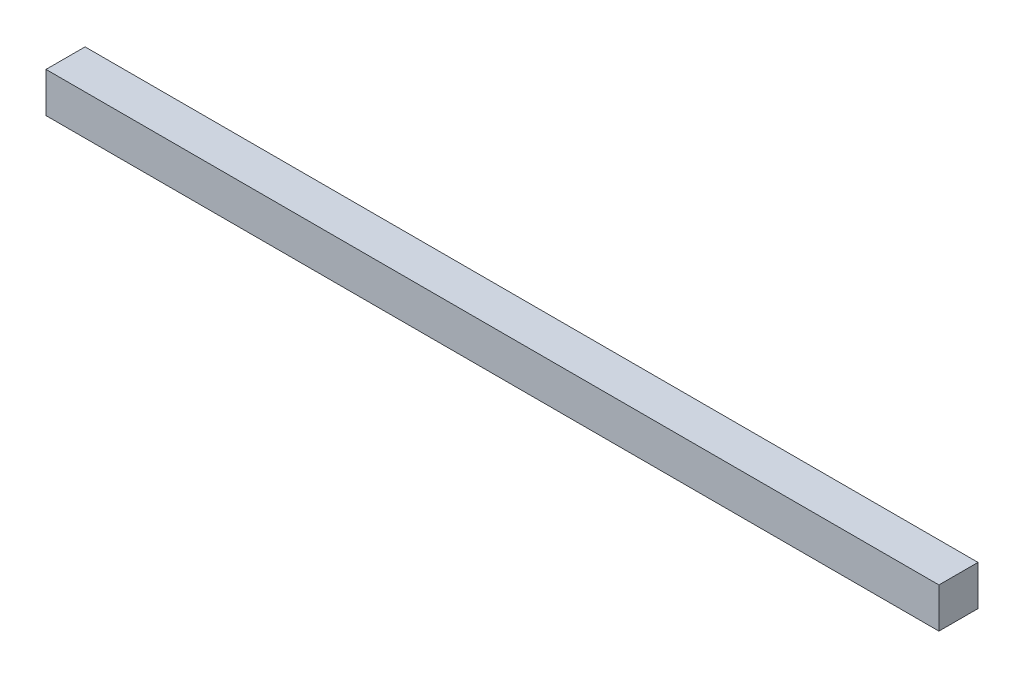
SolidWorks part; units mm, degrees
ref_plane "Спереди" through (0, 0, 0) normal (0, 0, 1) x (1, 0, 0)
ref_plane "Сверху" through (0, 0, 0) normal (0, 1, 0) x (1, 0, 0)
ref_plane "Справа" through (0, 0, 0) normal (1, 0, 0) x (0, 0, -1)
other "Configuration Table"
sketch "Ширина_фанера_плюс_зазор" plane through (0, 0, 0) normal (0, 0, 1) x (1, 0, 0)
  line L0 (-0.1, -3.075) -> (137.075, -3.075)
  line L1 (137.075, -3.075) -> (137.075, 3.075)
  line L2 (137.075, 3.075) -> (-0.1, 3.075)
  line L3 (-0.1, 3.075) -> (-0.1, -3.075)
  line L4 (-0.1, -3.075) -> (137.075, 3.075) construction
  point P4 (68.4875, 0)
  dimension "Ширина" = 137.175
  dimension "Глубина" = 6.15
  dimension "Положение_ПоОси" = 68.4875
extrude "Прямой_участок" add sketch "Ширина_фанера_плюс_зазор" along normal blind 6
equation "\"D1@Прямой_участок\" = \"Толщина тонких панелей\""
equation "\"Глубина@Ширина_фанера_плюс_зазор\"  = \"Толщина горизонтальных плит\"+\"Посадочный зазор\""
equation "\"Фанера\"= \"Толщина горизонтальных плит\""
equation "\"Ширина шипа\"=16"
equation "\"Межосевое шипов\"=40"
equation "\"Посадочный зазор\"=0.15"
equation "\"Основная фреза\"=6"
equation "\"Мелкая фреза\"=6"
equation "\"Запас разгрузки\"=0.05"
equation "\"Ширина образца\"=84"
equation "\"Высота образца\"=50"
equation "\"Канал М6\"=6"
equation "\"Гайка под ключ\"=10.3"
equation "\"Длина кармана гайки\"=6.2"
equation "\"Отступ гайки\"=12"
equation "\"Ширина@Ширина_фанера_плюс_зазор\" = (\"Глубина ячейки\"+3*\"Толщина тонких панелей\")/2+(\"Толщина вертикальных стенок\"+\"Посадочный зазор\")/2+0.1"
equation "\"Положение_ПоОси@Ширина_фанера_плюс_зазор\" = (\"Глубина ячейки\"+3*\"Толщина тонких панелей\")/4+(\"Толщина вертикальных стенок\"+\"Посадочный зазор\")/4-0.05"
equation "\"Ширина груза\"= 160"
equation "\"Глубина груза\"= 240"
equation "\"Высота груза\"= 160"
equation "\"Ширина ячейки\"= \"Ширина груза\" + 10"
equation "\"Глубина ячейки\"= \"Глубина груза\" + 10"
equation "\"Высота ячейки\"= \"Высота груза\" + 10 + 13"
equation "\"Колво ячеек ширина\"= 2"
equation "\"Колво ячеек высота\"= 2"
equation "\"Толщина стенки\"= \"Толщина тонких панелей\""
equation "\"Крепление дверцы\"= 5 "
equation "\"Ширина рейки\"= \"Толщина шестерни\""
equation "\"Высота рейки\"= 20"
equation "\"Высота пола\"= 2*\"Толщина тонких панелей\""
equation "\"Колво полозьев\"= 5"
equation "\"Отступ рейки\"= 20"
equation "\"Глубина каретки\"= \"Глубина ячейки\" + 30 + \"Мотор Y высота корпуса\" + 20"
equation "\"Длинна рейки\"= (\"Ширина ячейки\"+\"Толщина вертикальных стенок\"+\"Крепление дверцы\")*\"Колво ячеек ширина\"+\"Ширина ячейки выгрузки\"*\"Колво выгрузки\"+\"Толщина вертикальных стенок\"+2*\"Отступ крепления мотора фиксации\"-\"Крепление дверцы\"*\"Колво ячеек ширина\""
equation "\"Отступ шпильки\"= 26"
equation "\"Диаметр шпильки\"= 5"
equation "\"Длинна шпильки\"= (\"Высота ячейки\"+\"Толщина горизонтальных плит\"+\"Высота пола\")*\"Колво ячеек высота\"+2*(\"Толщина горизонтальных плит\"+\"Отступ рейки\")"
equation "\"Ширина пластины\"= 50  "
equation "\"Высота зона выгрузки\"= \"Высота ячейки\" * 2 + \"Толщина стенки\" * 2"
equation "\"Колво выгрузки\"= 1"
equation "\"Ширина ячейки выгрузки\"= \"Ширина ячейки\"+\"Толщина вертикальных стенок\"+2*\"Отступ крепления мотора фиксации\""
equation "\"Отступ крепления мотора фиксации\"= (\"Ширина пластины\"+20-\"Толщина вертикальных стенок\")/2"
equation "\"Мотор X ширина корпуса\"= 42.3"
equation "\"Мотор X высота корпуса\"= 42.3"
equation "\"Мотор X длина корпуса\"= 40"
equation "\"Мотор X вылет вала\"= 19.8"
equation "\"Мотор Y ширина корпуса\"= 42.3"
equation "\"Мотор Y высота корпуса\"= 42.3"
equation "\"Мотор Y длина корпуса\"= 48"
equation "\"Мотор Y вылет вала\"= 30"
equation "\"Мотор Z ширина корпуса\"= 42"
equation "\"Мотор Z высота корпуса\"= 42"
equation "\"Мотор Z длина корпуса\"= 40"
equation "\"Мотор Z вылет вала\"= 23"
equation "\"Мотор диаметр вала ПРЕДВ\"= 5"
equation "\"Мотор шаг крепления ПРЕДВ\"= 31"
equation "\"Мотор диаметр отверстий ПРЕДВ\"= 3"
equation "\"Мотор глубина отверстий ПРЕДВ\"= 4.5"
equation "\"Мотор диаметр буртика ПРЕДВ\"= 22"
equation "\"Мотор высота буртика ПРЕДВ\"= 2"
equation "\"Мотор диаметр шкива ПРЕДВ\"= 16"
equation "\"Мотор длина шкива ПРЕДВ\"= 12"
equation "\"Мотор отступ шкива ПРЕДВ\"= 5"
equation "\"Мотор X шаг градусов\"= 1.8"
equation "\"Мотор Y шаг градусов\"= 1.8"
equation "\"Мотор Z шаг градусов\"= 1.8"
equation "\"Мотор Y диаметр ротора\"= 25.78"
equation "\"Толщина шестерни\"= 10"
equation "\"Толщина тонких панелей\"= 6"
equation "\"Толщина вертикальных стенок\"= 6"
equation "\"Толщина горизонтальных плит\"= 6"
equation "\"Базовая высота корпуса\"= (\"Высота ячейки\"+\"Толщина тонких панелей\"+\"Высота пола\")*\"Колво ячеек высота\"+6*\"Толщина тонких панелей\"+\"Мотор X ширина корпуса\"+\"Мотор Y ширина корпуса\"+75"
equation "\"Высота корпуса\"= (\"Высота ячейки\"+\"Толщина горизонтальных плит\"+\"Высота пола\")*\"Колво ячеек высота\"+2*\"Толщина горизонтальных плит\"+4*\"Толщина тонких панелей\"+\"Мотор X ширина корпуса\"+\"Мотор Y ширина корпуса\"+75"
equation "\"Смещение центра корпуса\"= (\"Высота корпуса\"-\"Базовая высота корпуса\")/2-(\"Толщина горизонтальных плит\"-\"Толщина тонких панелей\")"
equation "\"Отметка пола\"= -\"Базовая высота корпуса\"/2+\"Толщина тонких панелей\""
equation "\"Отметка потолка\"= \"Отметка пола\"+\"Высота корпуса\"-2*\"Толщина горизонтальных плит\""
equation "\"Отметка верхней полки\"= \"Отметка потолка\"-(28+\"Толщина тонких панелей\")-\"Высота ячейки\"-\"Высота пола\""
equation "\"Отметка нижней полки\"= \"Отметка верхней полки\"-\"Высота ячейки\"-\"Высота пола\"-\"Толщина горизонтальных плит\""
